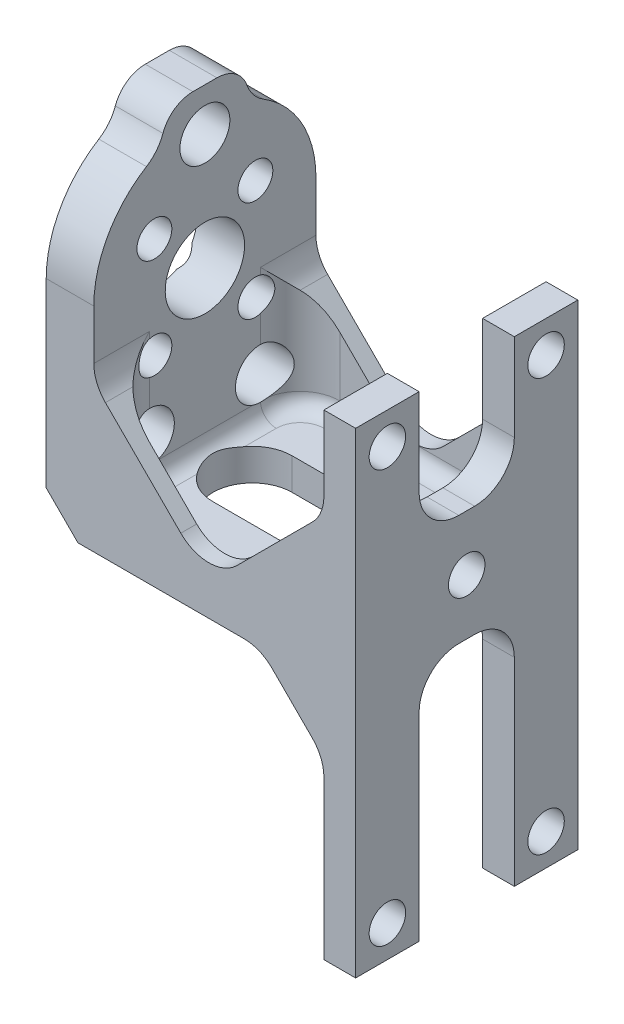
SolidWorks part; units mm, degrees
ref_plane "Front Plane" through (0, 0, 0) normal (0, 0, 1) x (1, 0, 0)
ref_plane "Top Plane" through (0, 0, 0) normal (0, 1, 0) x (1, 0, 0)
ref_plane "Right Plane" through (0, 0, 0) normal (1, 0, 0) x (0, 0, -1)
sketch "Sketch1" plane through (0, 0, 0) normal (0, 1, 0) x (1, 0, 0)
  line L0 (-7.25, 7) -> (7.25, -7) construction
  line L1 (-7.25, 7) -> (7.25, 7)
  line L2 (-7.25, 7) -> (-7.25, -7)
  line L3 (-7.25, -7) -> (7.25, -7)
  line L4 (7.25, 7) -> (7.25, -7)
  dimension "D2" = 14.5
  dimension "D1" = 14
extrude "base" add sketch "Sketch1" along normal blind 2
sketch "Sketch3" plane through (0, 0, 7) normal (0, 0, 1) x (1, 0, 0)
  line L0 (-7.25, 2) -> (7.25, 2) construction
  line L1 (-7.25, 0) -> (-10.25, 0)
  line L2 (-7.25, 0) -> (-7.25, 19)
  line L3 (-7.25, 19) -> (-10.25, 19)
  line L4 (-10.25, 0) -> (-10.25, 19)
  dimension "D1" = 3
  dimension "D2" = 17
extrude "motorFlange" add sketch "Sketch3" against normal up to surface (14 mm away) up to face at (0, 1, -7)
hole_wizard "CSK for M2 Flat Head Machine Screw1" positions "Sketch6" profile "Sketch7" countersink size "M2" standard "ANSI Metric"
sketch "Sketch6" plane through (-10.25, 0, 0) normal (-1, 0, 0) x (0, 0, 1)
  line L1 (-3.182, 15.182) -> (3.182, 15.182)
  line L2 (-3.182, 15.182) -> (-3.182, 8.818)
  line L3 (-3.182, 8.818) -> (3.182, 8.818)
  line L4 (3.182, 15.182) -> (3.182, 8.818)
  line L5 (0, 15.182) -> (0, 19)
  line L7 (-7, 19) -> (7, 19) construction
  line L8 (-3.182, 15.182) -> (3.182, 8.818) construction
  point P0 (-3.182, 15.182)
  point P2 (-3.182, 8.818)
  point P4 (3.182, 8.818)
  point P6 (3.182, 15.182)
  point P121 (0, 19)
  point P129 (0, 12)
  dimension "D3" = 7
  dimension "D1" = 9
sketch "Sketch7" plane through (-10.25, 15.182, -3.182) normal (0, 1, 0) x (0, 0, 1)
  line L0 (0, 0) -> (0, 5.8609)
  line L1 (0, 5.8609) -> (1.1, 5.2)
  line L2 (1.1, 5.2) -> (1.1, 1.1)
  line L3 (1.1, 1.1) -> (2.2, 0)
  line L5 (2.2, 0) -> (0, 0)
  line L6 (-1.1, 1.1) -> (-2.2, 0) construction
  line L10 (0, 5.8609) -> (-1.1, 5.2) construction
  line L11 (0, -6.35) -> (0, 107.95) construction
  dimension "Hole Dia." = 2.2
  dimension "Hole Depth" = 5.2
  dimension "Near C'Sink Dia." = 4.4
  dimension "Near C'Sink Angle" = 90
  dimension "Drill Angle" = 118
sketch "Sketch16" plane through (-10.25, 0, 0) normal (-1, 0, 0) x (0, 0, 1)
  line L0 (-3.182, 15.182) -> (3.182, 8.818) construction
  circle A0 centre (0, 12) radius 2.5
  dimension "D1" = 5
extrude "Cut-Extrude1" cut sketch "Sketch16" against normal blind 10
sketch "Sketch17" plane through (0, 19, 0) normal (0, 1, 0) x (1, 0, 0)
  line L0 (-7.25, 7) -> (-7.25, -7) construction
  line L1 (-10.25, 7) -> (-10.25, -7) construction
  line L2 (-7.25, -2.5) -> (-10.25, -2.5)
  line L3 (-7.25, -2.5) -> (-7.25, 2.5)
  line L4 (-7.25, 2.5) -> (-10.25, 2.5)
  line L5 (-10.25, -2.5) -> (-10.25, 2.5)
  point P8 (-7.25, 0)
  dimension "D1" = 5
extrude "Boss-Extrude5" add sketch "Sketch17" along normal blind 3
sketch "Sketch18" plane through (0, 2, 0) normal (0, 1, 0) x (1, 0, 0)
  line L0 (-7.25, 7) -> (-7.25, -7) construction
  line L1 (-7.25, 2.5) -> (-2.25, 2.5)
  line L2 (-7.25, 2.5) -> (-7.25, -2.5)
  line L3 (-7.25, -2.5) -> (-2.25, -2.5)
  line L4 (-2.25, 2.5) -> (-2.25, -2.5)
  point P6 (-7.25, 0)
  dimension "D1" = 5
  dimension "D2" = 5
extrude "Cut-Extrude2" [suppressed] cut sketch "Sketch18" against normal through all both and the other way through all
sketch "Sketch23" plane through (0, 0, 7) normal (0, 0, 1) x (1, 0, 0)
  line L0 (-10.25, 0) -> (10.554, -20.804) construction
  line L1 (-10.25, 0) -> (7.25, 0) construction
  dimension "D1" = 45
sketch "Sketch4" plane through (0, 0, 7) normal (0, 0, 1) x (1, 0, 0)
  line L1 (7.25, 0) -> (9.25, 0)
  line L2 (7.25, 0) -> (7.25, 7)
  line L3 (7.25, 7) -> (9.25, 7)
  line L4 (9.25, 0) -> (9.25, 7)
  line L5 (-7.25, 2) -> (7.25, 2) construction
  dimension "D1" = 2
  dimension "D2" = 5
extrude "Boss-Extrude3" add sketch "Sketch4" against normal up to surface (14 mm away) up to face at (-3.4167, 7, -7)
sketch "Sketch13" plane through (0, 7, 0) normal (0, 1, 0) x (1, 0, 0)
  line L0 (7.25, 7) -> (7.25, -7) construction
  line L1 (9.25, -7) -> (7.25, -7)
  line L2 (9.25, -7) -> (9.25, -3)
  line L3 (9.25, -3) -> (7.25, -3)
  line L4 (7.25, -7) -> (7.25, -3)
  dimension "D1" = 4
extrude "Boss-Extrude4" add sketch "Sketch13" along normal blind 8
mirror "Mirror5" about plane through (0, 0, 0) normal (0, 0, 1) of "Boss-Extrude4"
sketch "Sketch22" plane through (0, 0, 0) normal (0, -1, 0) x (1, 0, 0)
  line L1 (9.25, 7) -> (7.25, 7)
  line L2 (9.25, 7) -> (9.25, 3)
  line L3 (9.25, 3) -> (7.25, 3)
  line L4 (7.25, 7) -> (7.25, 3)
  line L5 (9.25, -7) -> (7.25, -7)
  line L6 (9.25, -7) -> (9.25, -3)
  line L7 (9.25, -3) -> (7.25, -3)
  line L8 (7.25, -7) -> (7.25, -3)
extrude "Boss-Extrude6" add sketch "Sketch22" along normal blind 15
sketch "Sketch26" plane through (0, 0, 7) normal (0, 0, 1) x (1, 0, 0)
  line L0 (-7.25, 9.25) -> (0, 2)
  line L1 (-7.25, 2) -> (-7.25, 19) construction
  line L2 (-7.25, 2) -> (7.25, 2) construction
  dimension "D1" = 45
rib "Rib3" sketch "Sketch26" sketch "Sketch26" thickness 1 extrusion direction parallel to sketch draft on no parameters "D1"=1
sketch "Sketch27" plane through (0, 0, 7) normal (0, 0, 1) x (1, 0, 0)
  line L0 (0, 2) -> (7.25, 9.25)
  line L1 (7.25, 15) -> (7.25, 2) construction
rib "Rib4" sketch "Sketch27" sketch "Sketch27" thickness 1 extrusion direction parallel to sketch draft on no parameters "D1"=1
sketch "Sketch28" plane through (0, 0, 7) normal (0, 0, 1) x (1, 0, 0)
  line L0 (3.25, 0) -> (7.25, -4)
  line L1 (-10.25, 0) -> (7.25, 0) construction
  line L2 (7.25, -15) -> (7.25, 0) construction
  dimension "D1" = 45
  dimension "D2" = 4
rib "Rib7" sketch "Sketch28" sketch "Sketch28" thickness 1 extrusion direction parallel to sketch draft on no parameters "D1"=1
mirror "Mirror7" about plane through (0, 0, 0) normal (0, 0, 1) of "Rib7", "Rib4", "Rib3"
fillet "Fillet5" radius 2.5 2 edges at (-8.75, 19, 2.5) (-8.75, 19, -2.5)
fillet "Fillet1" radius 7 2 edges at (-8.75, 19, -7) (-8.75, 19, 7)
fillet "Fillet6" radius 2 2 edges at (-8.75, 22, 2.5) (-8.75, 22, -2.5)
fillet "Fillet4" radius 2.5 2 edges at (8.25, 7, -3) (8.25, 7, 3)
fillet "Fillet8" radius 2.5 8 edges at (8.25, 0, -3) (8.25, 0, 3) (7.25, -4, -6.5) (3.25, 0, -6.5) (7.25, -4, 6.5) (3.25, 0, 6.5) (7.25, -2, 6) (7.25, -2, -6)
fillet "Fillet7" radius 1 6 edges at (7.25, 0, -2) (7.25, 0, 2) (3.4822, 0, -6) (3.4822, 0, 6) (6.5178, 0, 5.2678) (6.5178, 0, -5.2678)
fillet "Fillet13" radius 2.5 10 edges at (0, 2, 6.5) (-7.25, 9.25, 6.5) (-7.25, 5.625, 6) (-7.25, 5.625, -6) (7.25, 5.625, -6) (7.25, 5.625, 6) (7.25, 9.25, 6.5) (7.25, 9.25, -6.5) (-7.25, 9.25, -6.5) (0, 2, -6.5)
fillet "Fillet11" radius 1 10 edges at (7.25, 2, 0) (-7.25, 2, 0) (-6.5178, 2, 5.2678) (-6.5178, 2, -5.2678) (-2.375, 2, 6) (2.375, 2, 6) (2.375, 2, -6) (-2.375, 2, -6) (6.5178, 2, -5.2678) (6.5178, 2, 5.2678)
sketch "Sketch21" plane through (0, 2, 0) normal (0, 1, 0) x (1, 0, 0)
  line L1 (-7.25, -3.5) -> (-7.25, 3.5) construction
  circle A0 centre (-3.75, 0) radius 2.5
  point P5 (-7.25, 0)
  point P6 (-6.25, 0)
  dimension "D1" = 5
  dimension "D2" = 1
extrude "wireHole" [suppressed] cut sketch "Sketch21" against normal through all both and the other way through all
sketch "Sketch25" plane through (0, 2, 0) normal (0, 1, 0) x (1, 0, 0)
  line L0 (-4.25, 0) -> (0.75, 0) construction
  line L1 (-4.25, 2.5) -> (0.75, 2.5)
  line L2 (-4.25, -2.5) -> (0.75, -2.5)
  line L3 (-7.25, -3.5) -> (-7.25, 3.5) construction
  arc A0 (-4.25, 2.5) -> (-4.25, -2.5) centre (-4.25, 0) ccw
  arc A1 (0.75, -2.5) -> (0.75, 2.5) centre (0.75, 0) ccw
  point P3 (-1.75, 0)
  point P8 (-6.75, 0)
  point P13 (-7.25, 0)
  dimension "D2" = 5
  dimension "D3" = 2.5
  dimension "D1" = 0.5
extrude "wireSlot" cut sketch "Sketch25" against normal through all both and the other way through all
chamfer "Chamfer1" distance 2 angle 45 1 edges at (-10.25, 0, 0)
hole_wizard "Tapped Hole for M2.2x0.45 Helicoil1" positions "Sketch14" profile "Sketch15" tap size "M2.2x0.45" standard "Helicoil® Metric"
sketch "Sketch14" plane through (9.25, 0, 0) normal (1, 0, 0) x (0, 0, -1)
  line L0 (-5, 15) -> (-5, 13) construction
  line L1 (-7, 15) -> (-3, 15) construction
  line L3 (0, 7) -> (0, 0) construction
  line L6 (0.5, 0) -> (-0.5, 0) construction
  line L7 (-5, 13) -> (-7, 13) construction
  line L8 (-7, -15) -> (-7, 15) construction
  line L16 (-5, -15) -> (-5, -13) construction
  line L17 (-3, -15) -> (-7, -15) construction
  line L18 (0.5, 7) -> (-0.5, 7) construction
  point P0 (-5, 13)
  point P41 (0, 3.5)
  point P42 (5, 13)
  point P54 (-5, -13)
  point P60 (5, -13)
sketch "Sketch15" plane through (9.25, 13, 5) normal (0, 1, 0) x (0, 0, -1)
  line L0 (0, 0) -> (0, 6.691)
  line L1 (0, 6.691) -> (1.15, 6)
  line L2 (1.15, 6) -> (1.15, 0)
  line L5 (1.15, 0) -> (0, 0)
  line L10 (0, 6.691) -> (-1.15, 6) construction
  line L11 (0, -6.35) -> (0, 107.95) construction
  dimension "Tap Drill Dia." = 2.3
  dimension "Tap Drill Depth" = 6
  dimension "Drill Angle" = 118
cosmetic thread "Hole Thread7" parameters "D1"=2, "D2"=2.845
cosmetic thread "Hole Thread8" parameters "D1"=2.7, "D2"=2.845
cosmetic thread "Hole Thread9" parameters "D1"=2.7, "D2"=2.845
cosmetic thread "Hole Thread11" parameters "D1"=2.7, "D2"=2.845
cosmetic thread "Hole Thread12" parameters "D1"=2.7, "D2"=2.845
hole_wizard "Tapped Hole for M3x0.5 Helicoil1" positions "Sketch11" profile "Sketch12" tap size "M3x0.5" standard "Helicoil® Metric"
sketch "Sketch11" plane through (-10.25, 0, 0) normal (-1, 0, 0) x (0, 0, 1)
  line L0 (0, 0) -> (0, 19.2948) construction
  line L1 (-7, 0) -> (7, 0) construction
  line L2 (1.8358, 16.922) -> (0, 19.2948) construction
  line L4 (3.0416, 17.855) -> (0.6299, 15.9891) construction
  arc A0 (2.1803, 13.2233) -> (1.2233, 14.1803) centre (3.182, 15.182) ccw construction
  point P0 (3.5, 4.5)
  point P4 (0, 19.2948)
  point P16 (-3.5, 4.5)
  point P33 (1.8358, 16.922)
  dimension "D1" = 7
  dimension "D2" = 3
  dimension "D3" = 4.5
cosmetic thread "Hole Thread2" parameters "D1"=3.5, "D2"=3.716
cosmetic thread "Hole Thread3" parameters "D1"=3.5, "D2"=3.716
sketch "Sketch12" plane through (-10.25, 4.5, 3.5) normal (0, 1, 0) x (0, 0, 1)
  line L0 (0, 0) -> (0, 8.4464)
  line L1 (0, 8.4464) -> (1.575, 7.5)
  line L2 (1.575, 7.5) -> (1.575, 0)
  line L5 (1.575, 0) -> (0, 0)
  line L10 (0, 8.4464) -> (-1.575, 7.5) construction
  line L11 (0, -6.35) -> (0, 107.95) construction
  dimension "Tap Drill Dia." = 3.15
  dimension "Tap Drill Depth" = 7.5
  dimension "Drill Angle" = 118
cosmetic thread "Hole Thread10" parameters "D1"=3, "D2"=3.716
sketch "Sketch29" plane through (0, 15, 0) normal (0, 1, 0) x (1, 0, 0)
  line L4 (9.25, -7) -> (9.25, -3)
  line L5 (9.25, -3) -> (7.25, -3)
  line L6 (7.25, -3) -> (7.25, -7)
  line L7 (7.25, -7) -> (9.25, -7)
  line L8 (9.25, -7) -> (9.25, -3)
  line L9 (9.25, -3) -> (7.25, -3)
  line L10 (7.25, -3) -> (7.25, -7)
  line L11 (7.25, -7) -> (9.25, -7)
  line L12 (9.25, 7) -> (7.25, 7)
  line L13 (7.25, 7) -> (7.25, 3)
  line L14 (7.25, 3) -> (9.25, 3)
  line L15 (9.25, 3) -> (9.25, 7)
  line L16 (9.25, 7) -> (7.25, 7)
  line L17 (7.25, 7) -> (7.25, 3)
  line L18 (7.25, 3) -> (9.25, 3)
  line L19 (9.25, 3) -> (9.25, 7)
  dimension "D1" = 0
  dimension "D2" = 0
extrude "Boss-Extrude7" [suppressed] add sketch "Sketch29" along normal blind 20
equation "\"motorDiameter\"= 14mm"
equation "\"baseThickness\"= 2mm"
equation "\"motorWallThickness\"= 3mm"
equation "\"boardWallThickness\"= \"baseThickness\""
equation "\"D1@base\" = \"baseThickness\""
equation "\"motorLength\"= 12.5mm"
equation "\"magnetHeight\"= 2mm"
equation "\"rotorClearance\"= 3mm"
equation "\"D1@Sketch3\"=\"motorWallThickness\""
equation "\"D2@Sketch3\"=\"motorDiameter\"+\"rotorClearance\""
equation "\"D1@Sketch4\"=\"boardWallThickness\""
equation "\"D1@Fillet1\"=\"motorDiameter\"/2"
equation "\"D3@Sketch6\"=\"motorDiameter\"/2"
equation "\"encoderClearance\"= 5mm"
equation "\"D2@Sketch4\"=\"motorDiameter\"/2+\"rotorClearance\"-\"encoderClearance\""
equation "\"cutterOD\"= 5mm"
equation "\"cutterSnubRadius\"= 1mm"
equation "\"D1@Fillet4\"= \"cutterOD\" / 2"
equation "\"D1@Sketch1\"=\"motorDiameter\""
equation "\"encoderClearance_vertical\"= 1mm"
equation "\"encoderHeight\"= 1mm"
equation "\"encoderWidth\"= 2mm"
equation "\"D2@Sketch1\"=\"motorLength\"+\"magnetHeight\"+\"encoderHeight\"+\"encoderClearance_vertical\"-\"boardWallThickness\""
equation "\"D1@Fillet5\"=\"cutterOD\"/2"
equation "\"D1@Fillet8\"=\"cutterOD\"/2"
equation "\"D1@Fillet11\"=\"cutterSnubRadius\""
equation "\"D1@Fillet7\"=\"cutterOD\"/2"
equation "\"D3@Sketch25\"=\"cutterOD\"/2"
equation "\"D1@Fillet7\"=\"cutterSnubRadius\"+0"
equation "\"D1@Fillet13\"=\"cutterOD\"/2"
